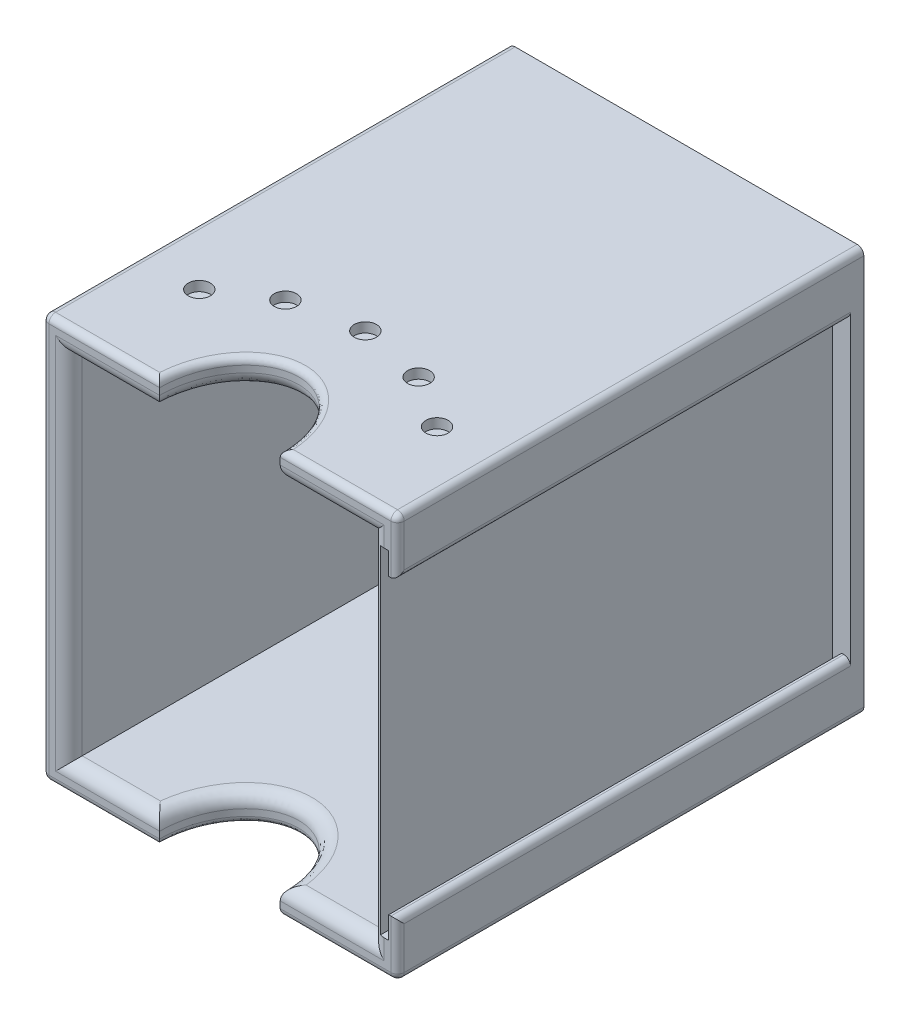
SolidWorks part; units mm, degrees
ref_plane "Front Plane" through (0, 0, 0) normal (1, 0, 0) x (0, 1, 0)
ref_plane "Top Plane" through (0, 0, 0) normal (0, 0, 1) x (0, 1, 0)
ref_plane "Right Plane" through (0, 0, 0) normal (0, 1, 0) x (-1, 0, 0)
sketch "Sketch2" plane through (0, 0, 0) normal (0, 0, 1) x (0, 1, 0)
  line L1 (-39.5, -34) -> (39.5, -34)
  line L2 (-39.5, -34) -> (-39.5, 34)
  line L3 (-39.5, 34) -> (39.5, 34)
  line L4 (39.5, -34) -> (39.5, 34)
  line L5 (-39.5, -34) -> (39.5, 34) construction
  line L6 (-39.5, 34) -> (39.5, -34) construction
  line L7 (-41.5, -36) -> (41.5, -36)
  line L8 (-41.5, -36) -> (-41.5, 36)
  line L9 (-41.5, 36) -> (41.5, 36)
  line L10 (41.5, -36) -> (41.5, 36)
  line L11 (-41.5, -36) -> (41.5, 36) construction
  line L12 (-41.5, 36) -> (41.5, -36) construction
  line L13 (-45.5, -40) -> (45.5, -40)
  line L14 (-45.5, -40) -> (-45.5, 40)
  line L15 (-45.5, 40) -> (45.5, 40)
  line L16 (45.5, -40) -> (45.5, 40)
  line L17 (-45.5, -40) -> (45.5, 40) construction
  line L18 (-45.5, 40) -> (45.5, -40) construction
  point P0 (0, 0)
  point P6 (0, 0)
  point P11 (0, 0)
  dimension "D1" = 79
  dimension "D2" = 68
  dimension "D3" = 2
  dimension "D4" = 2
  dimension "D5" = 4
  dimension "D6" = 4
extrude "Boss-Extrude1" add sketch "Sketch2" along normal blind 105 contours L7 L10 L9 L8 L4 L1 L2 L3 | L13 L16 L15 L14 L10 L7 L8 L9 region at (0, -40.4012, 0) region at (0, -44.2883, 0)
sketch "Sketch3" plane through (0, 0, 0) normal (0, 0, 1) x (0, 1, 0)
  line L1 (-39.5, -34) -> (39.5, -34)
  line L2 (-39.5, -34) -> (-39.5, 34)
  line L3 (-39.5, 34) -> (39.5, 34)
  line L4 (39.5, -34) -> (39.5, 34)
  line L5 (-39.5, -34) -> (39.5, 34) construction
  line L6 (-39.5, 34) -> (39.5, -34) construction
  point P0 (0, 0)
  dimension "D1" = 79
  dimension "D2" = 68
extrude "Boss-Extrude2" add sketch "Sketch3" along normal blind 12
sketch "Sketch4" plane through (0, 0, 0) normal (0, 1, 0) x (-1, 0, 0)
  line L1 (-40, 105) -> (40, 105) construction
  ellipse E0 centre (0, 105) end of major axis (0, 122.7695) minor radius 13.5815
extrude "Cut-Extrude1" cut sketch "Sketch4" against normal mid plane 100
sketch "Sketch7" plane through (0, 0, 0) normal (0, 0, 1) x (0, 1, 0)
  line L0 (0, -40) -> (33, -40)
  line L1 (-45.5, -40) -> (45.5, -40) construction
  line L2 (0, -40) -> (-33, -40)
  line L3 (-33, -40) -> (-33, -38)
  line L4 (33, -40) -> (33, -38)
  line L5 (33, -38) -> (38, -38)
  line L6 (38, -38) -> (38, -36)
  line L7 (38, -36) -> (-38, -36)
  line L8 (-33, -38) -> (-38, -38)
  line L9 (-38, -38) -> (-38, -36)
  dimension "D1" = 33
  dimension "D2" = 33
  dimension "D3" = 2
  dimension "D4" = 5
  dimension "D5" = 2
  dimension "D6" = 76
extrude "Cut-Extrude2" cut sketch "Sketch7" against normal blind 102 from surface starting at face at (25.2908, 0, 105)
fillet "Fillet1" radius 3 8 edges at (0, 39.5, 87.2305) (-23.7908, 39.5, 105) (23.7908, 39.5, 105) (34, 0, 105) (-34, 0, 105) (-23.7908, -39.5, 105) (0, -39.5, 87.2305) (23.7908, -39.5, 105)
fillet "Fillet2" radius 1.5 15 edges at (40, 33, 54) (-40, 45.5, 52.5) (40, 45.5, 52.5) (40, 39.25, 105) (26.7908, 45.5, 105) (0, 45.5, 87.2305) (-26.7908, 45.5, 105) (-40, 0, 105) (-40, -45.5, 52.5) (40, -45.5, 52.5) (40, -33, 54) (40, -39.25, 105) (-26.7908, -45.5, 105) (0, -45.5, 87.2305) (26.7908, -45.5, 105)
sketch "Sketch8" plane through (0, 0, 0) normal (0, 1, 0) x (-1, 0, 0)
  line L0 (-26.768, 103.5) -> (-26.768, 41.2386) construction
  line L1 (-15.036, 103.5) -> (-38.5, 103.5) construction
  line L2 (26.768, 103.5) -> (26.768, 41.2386) construction
  line L3 (38.5, 103.5) -> (15.036, 103.5) construction
  circle A0 centre (0, 72.2471) radius 2.5
  circle A1 centre (26.768, 82.8671) radius 2.5
  circle A2 centre (-26.768, 82.8671) radius 2.5
  circle A3 centre (15, 75.2471) radius 2.5
  circle A4 centre (-15, 75.2471) radius 2.5
  ellipse E0 centre (0, 105) end of major axis (0, 122.7695) minor radius 13.5815 (-13.5815, 105) -> (13.5815, 105) ccw construction
  dimension "D1" = 5
  dimension "D2" = 5
  dimension "D3" = 5
  dimension "D4" = 5
  dimension "D5" = 5
  dimension "D6" = 26.768
  dimension "D7" = 15
  dimension "D8" = 15
  dimension "D9" = 32.7529
  dimension "D10" = 3
  dimension "D11" = 3
  dimension "D12" = 7.62
  dimension "D13" = 7.62
extrude "Cut-Extrude4" cut sketch "Sketch8" along normal blind 2.2 from surface starting at face at (0, -45.5, 66.0384)
sketch "Sketch14" plane through (0, 0, 0) normal (0, 1, 0) x (-1, 0, 0)
  line L0 (26.768, 103.5) -> (26.768, 44.4512) construction
  line L1 (38.5, 103.5) -> (15.036, 103.5) construction
  line L2 (-15.036, 103.5) -> (-38.5, 103.5) construction
  line L3 (-26.768, 103.5) -> (-26.768, 53.8096) construction
  circle A0 centre (0, 72.25) radius 2.5
  circle A1 centre (15, 75.25) radius 2.5
  circle A2 centre (26.768, 82.87) radius 2.5
  circle A3 centre (-15, 75.25) radius 2.5
  circle A4 centre (-26.768, 82.87) radius 2.5
  ellipse E0 centre (0, 105) end of major axis (0, 122.7695) minor radius 13.5815 (-13.5815, 105) -> (13.5815, 105) ccw construction
  dimension "D1" = 5
  dimension "D2" = 5
  dimension "D3" = 5
  dimension "D4" = 5
  dimension "D5" = 5
  dimension "D6" = 32.75
  dimension "D7" = 15
  dimension "D8" = 15
  dimension "D9" = 0
  dimension "D10" = 0
  dimension "D11" = 7.62
  dimension "D12" = 7.62
  dimension "D13" = 26.768
  dimension "D14" = 3
  dimension "D15" = 3
extrude "Cut-Extrude5" cut sketch "Sketch14" against normal blind 2.2 from surface starting at face at (0, 45.5, 66.0384)
